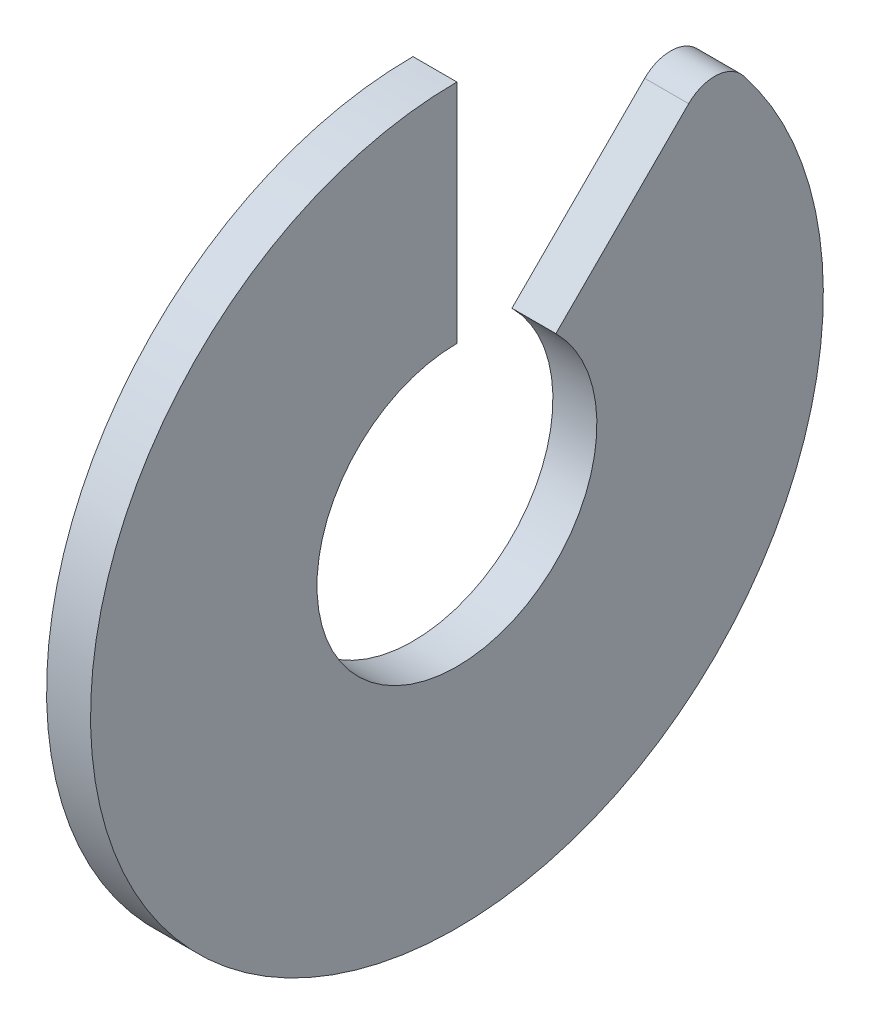
SolidWorks part; units mm, degrees
note: The reader was unsure of these and kept them because the rebuilt part matched: thickness of "Базовая кромка1", "Листовой металл3".
material "09Г2С ГОСТ 4543-71"
ref_plane "Спереди" through (0, 0, 0) normal (0, 0, 1) x (1, 0, 0)
ref_plane "Сверху" through (0, 0, 0) normal (0, 1, 0) x (1, 0, 0)
ref_plane "Справа" through (0, 0, 0) normal (1, 0, 0) x (0, 0, -1)
sketch "Эскиз1" plane through (0, 0, 0) normal (1, 0, 0) x (0, 0, -1)
  line L0 (0, 38.2) -> (0, 100)
  line L1 (27.0115, 27.0115) -> (70.7107, 70.7107)
  line L2 (0, 38.2) -> (0, 0) construction
  line L3 (0, 0) -> (27.0115, 27.0115) construction
  arc A0 (0, 38.2) -> (27.0115, 27.0115) centre (0, 0) ccw
  arc A1 (0, 100) -> (70.7107, 70.7107) centre (0, 0) ccw
  dimension "D1" = 45
  dimension "D2" = 100
  dimension "D3" = 38.2
base flange "Базовая кромка1" sketch "Эскиз1" thickness 12 reverse thickness direction no parameters "D1"=4
fillet "Скругление1" radius 10 1 edges at (-6, 70.7107, -70.7107)
sketch "Сгиб-Линии1" [suppressed] plane through (0, 0, 0) normal (0, 1, 0) x (1, 0, 0)
sketch "Граничная рамка1" [suppressed] plane through (0, 0, 0) normal (0, 1, 0) x (1, 0, 0)
sheet metal parameters "Листовой металл3" thickness 12 parameters "D1"=4
flat pattern "Развертка3" [suppressed]
sketch "Сгиб-Линии2" plane through (0, 0, 0) normal (0, 1, 0) x (1, 0, 0)
sketch3d "Граничная рамка2" [suppressed]
  line L0 (-52.3255, 124.4016, 0) -> (128.9336, 39.8729, 0) construction
  line L1 (-132.894, -48.3652, 0) -> (48.3652, -132.8939, 0) construction
  line L2 (-52.3255, 124.4016, 0) -> (-132.894, -48.3652, 0) construction
  line L3 (128.9336, 39.8729, 0) -> (48.3652, -132.8939, 0) construction
